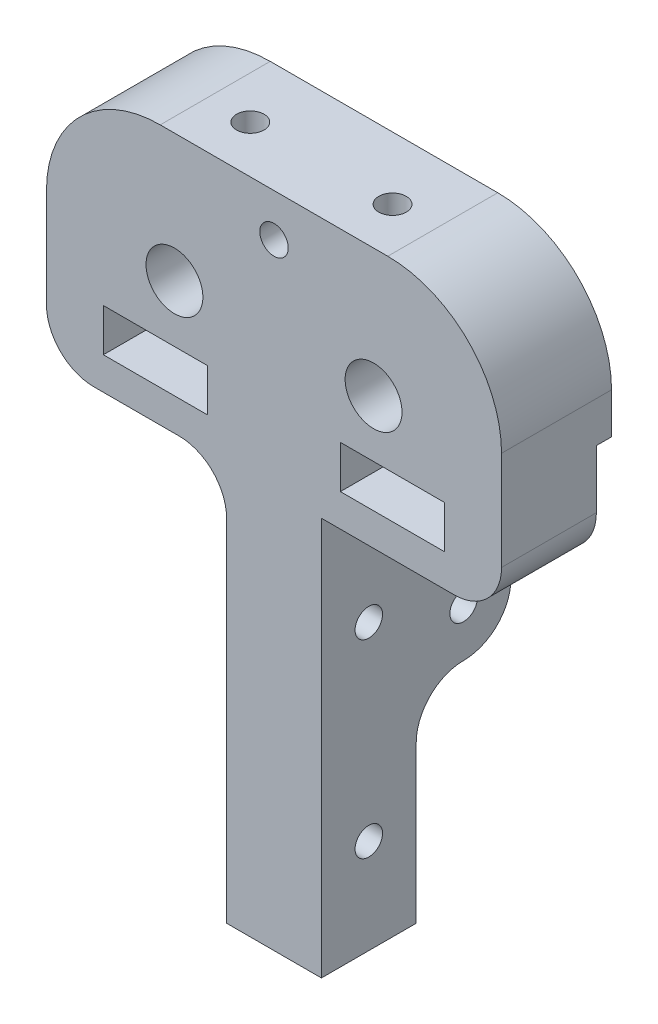
SolidWorks part; units mm, degrees
ref_plane "Front Plane" through (0, 0, 0) normal (0, 0, 1) x (1, 0, 0)
ref_plane "Top Plane" through (0, 0, 0) normal (0, 1, 0) x (1, 0, 0)
ref_plane "Right Plane" through (0, 0, 0) normal (1, 0, 0) x (0, 0, -1)
sketch "Sketch1" plane through (0, 0, 0) normal (0, 0, 1) x (1, 0, 0)
  line L1 (0, 0) -> (48, 0)
  line L2 (0, 0) -> (0, -70)
  line L3 (0, -70) -> (48, -70)
  line L4 (48, 0) -> (48, -70)
  dimension "D1" = 48
  dimension "D2" = 70
extrude "Boss-Extrude1" add sketch "Sketch1" along normal blind 10
sketch "Sketch2" plane through (0, 0, 10) normal (0, 0, 1) x (1, 0, 0)
  line L0 (0, 0) -> (0, -70) construction
  line L1 (48, 0) -> (0, 0) construction
  circle A0 centre (13.5, -13.5) radius 3
  circle A1 centre (34.5, -13.5) radius 3
  dimension "D1" = 6
  dimension "D2" = 6
  dimension "D3" = 21
  dimension "D4" = 13.5
  dimension "D5" = 13.5
  dimension "D6" = 13.5
extrude "Cut-Extrude1" cut sketch "Sketch2" against normal through all
sketch "Sketch3" plane through (0, 0, 10) normal (0, 0, 1) x (1, 0, 0)
  line L0 (0, 0) -> (0, -70) construction
  line L1 (13.7, -38.5) -> (34.3, -38.5)
  line L2 (13.7, -38.5) -> (13.7, -59.1)
  line L3 (13.7, -59.1) -> (34.3, -59.1)
  line L4 (34.3, -38.5) -> (34.3, -59.1)
  circle A0 centre (13.5, -13.5) radius 3 construction
  dimension "D1" = 20.6
  dimension "D2" = 20.6
  dimension "D3" = 13.7
  dimension "D4" = 25
extrude "Cut-Extrude2" cut sketch "Sketch3" against normal through all
fillet "Fillet1" radius 12 2 edges at (0, 0, 5) (48, 0, 5)
ref_plane "打印面" through (0, 0, -10) normal (0, 0, 1) x (1, 0, 0)
sketch "Sketch4" plane through (0, 0, 0) normal (0, 0, -1) x (-1, 0, 0)
  line L0 (-36, 0) -> (-12, 0) construction
  circle A0 centre (-24, -4.5) radius 1.5
  dimension "D1" = 3
  dimension "D2" = 4.5
extrude "Cut-Extrude3" cut sketch "Sketch4" against normal through all
sketch "Sketch5" plane through (0, 0, 0) normal (0, 1, 0) x (1, 0, 0)
  line L0 (36, -10) -> (12, -10) construction
  circle A0 centre (16.5, -5) radius 1.45
  circle A1 centre (31.5, -5) radius 1.45
  point P6 (24, -10)
  dimension "D1" = 2.9
  dimension "D3" = 5
  dimension "D4" = 7.5
extrude "Cut-Extrude4" cut sketch "Sketch5" against normal blind 10
sketch "Sketch7" plane through (0, 0, 0) normal (0, 0, -1) x (-1, 0, 0)
  line L0 (-48, -70) -> (-48, -12) construction
  line L1 (-42, -19.5) -> (-31, -19.5)
  line L2 (-42, -19.5) -> (-42, -24)
  line L3 (-42, -24) -> (-31, -24)
  line L4 (-31, -19.5) -> (-31, -24)
  line L5 (-24, 0) -> (-24, -28.6841) construction
  line L6 (-36, 0) -> (-12, 0) construction
  line L7 (-34.3, -38.5) -> (-13.7, -38.5) construction
  line L8 (-17, -19.5) -> (-17, -24)
  line L9 (-6, -24) -> (-17, -24)
  line L10 (-6, -19.5) -> (-6, -24)
  line L11 (-6, -19.5) -> (-17, -19.5)
  dimension "D1" = 4.5
  dimension "D2" = 11
  dimension "D3" = 6
  dimension "D4" = 14.5
extrude "Cut-Extrude5" cut sketch "Sketch7" against normal through all both and the other way through all
sketch "Sketch11" plane through (0, 0, 0) normal (0, 0, -1) x (-1, 0, 0)
  line L0 (-31, -24) -> (-42, -24) construction
  line L1 (-40, -27.5) -> (-8, -27.5)
  line L2 (-40, -27.5) -> (-40, -42.5)
  line L3 (-40, -42.5) -> (-8, -42.5)
  line L4 (-8, -27.5) -> (-8, -42.5)
  dimension "D1" = 15
  dimension "D2" = 3.5
  dimension "D3" = 2
  dimension "D4" = 2
extrude "Cut-Extrude6" cut sketch "Sketch11" against normal through all
sketch "Sketch12" plane through (0, -24, 0) normal (0, 1, 0) x (1, 0, 0)
  line L0 (31, 0) -> (42, 0) construction
  line L1 (6, 0) -> (17, 0) construction
  circle A0 centre (36.5, -3) radius 1.5
  circle A1 centre (11.5, -3) radius 1.5
  dimension "D1" = 3
  dimension "D3" = 3
extrude "Cut-Extrude7" cut sketch "Sketch12" against normal blind 5 and the other way blind 8
sketch "Sketch13" plane through (0, 0, 0) normal (0, 0, -1) x (-1, 0, 0)
  line L0 (-48, -70) -> (-48, -12) construction
  line L1 (-48, -16.3) -> (0, -16.3)
  line L2 (-48, -16.3) -> (-48, 0)
  line L3 (-48, 0) -> (0, 0)
  line L4 (0, -16.3) -> (0, 0)
  circle A0 centre (-34.5, -13.5) radius 3
  circle A1 centre (-13.5, -13.5) radius 3
  circle M10 centre (-24, -4.5) radius 1.5
  circle M19 centre (-34.5, -13.5) radius 3
  circle M20 centre (-13.5, -13.5) radius 3
  line M21 (0, -70) -> (0, -12)
  arc M22 (0, -12) -> (-12, 0) centre (-12, -12) ccw
  line M23 (-12, 0) -> (-36, 0)
  arc M24 (-36, 0) -> (-48, -12) centre (-36, -12) ccw
  line M25 (-48, -12) -> (-48, -70)
  dimension "D1" = 16.3
extrude "Boss-Extrude4" add sketch "Sketch13" along normal blind 1.6 contours L1 M25 M19 M20 M21 M22 M23 M24 M10 region at (24, -8.2505, 0)
fillet "Fillet2" radius 8 2 edges at (13.7, -42.5, 5) (34.3, -42.5, 5)
sketch "Sketch14" plane through (0, 0, 10) normal (0, 0, 1) x (1, 0, 0)
  line L0 (48, -70) -> (48, -12) construction
  line L1 (0, -70) -> (48, -70)
  line L2 (0, -70) -> (0, -27.4286)
  line L3 (0, -27.4286) -> (48, -27.4286)
  line L4 (48, -70) -> (48, -27.4286)
extrude "Cut-Extrude8" cut sketch "Sketch14" against normal through all
sketch "Sketch15" plane through (0, -27.4286, 0) normal (0, -1, 0) x (-1, 0, 0)
  line L0 (-48, 0) -> (0, 0) construction
  line L1 (-19, 0) -> (-29, 0)
  line L2 (-19, 0) -> (-19, -10)
  line L3 (-19, -10) -> (-29, -10)
  line L4 (-29, 0) -> (-29, -10)
  line L5 (-48, -10) -> (0, -10) construction
  point P8 (-24, 0)
  dimension "D1" = 10
  dimension "D2" = 24
extrude "Boss-Extrude5" add sketch "Sketch15" along normal blind 42
sketch "Sketch18" plane through (0, 0, 0) normal (0, 0, -1) x (-1, 0, 0)
  line L0 (-19, -69.4286) -> (-19, -27.4286) construction
  line L1 (-19, -37.9286) -> (-29, -37.9286)
  line L2 (-19, -37.9286) -> (-19, -47.9286)
  line L3 (-19, -47.9286) -> (-29, -47.9286)
  line L4 (-29, -37.9286) -> (-29, -47.9286)
  line L5 (-29, -69.4286) -> (-29, -27.4286) construction
  dimension "D1" = 10
  dimension "D2" = 21.5
extrude "Boss-Extrude8" add sketch "Sketch18" along normal blind 10
sketch "Sketch19" plane through (29, 0, 0) normal (1, 0, 0) x (0, 0, -1)
  line L0 (0, -69.4286) -> (-10, -69.4286) construction
  line L1 (10, -37.9286) -> (10, -47.9286) construction
  circle A0 centre (5, -42.9286) radius 1.45
  circle A1 centre (-5, -59.4286) radius 1.45
  circle A2 centre (-5, -39.4286) radius 1.45
  point P10 (10, -42.9286)
  dimension "D1" = 2.9
  dimension "D2" = 2.9
  dimension "D3" = 2.9
  dimension "D4" = 10
  dimension "D5" = 20
extrude "Cut-Extrude9" cut sketch "Sketch19" against normal through all
fillet "Fillet3" radius 5 3 edges at (0, -27.4286, 5) (19, -27.4286, 5) (48, -27.4286, 5)
fillet "Fillet4" radius 5 3 edges at (24, -47.9286, 0) (24, -47.9286, -10) (24, -37.9286, -10)
fillet "Fillet5" radius 2 1 edges at (24, -37.9286, 0)
equation "\"D3@Sketch3\"=(\"D1@Sketch1\"-\"D1@Sketch3\")/2"
equation "\"滑动-垂直孔\"= 0.6"
equation "\"滑动-水平孔\"= 0.3"
equation "\"松动-垂直孔\"= 0.3"
equation "\"松动-水平孔\"= 0.1"
equation "\"正常-垂直孔\"= 0.15"
equation "\"正常-水平孔\"= 0"
equation "\"紧缩-垂直孔\"= 0"
equation "\"紧缩-水平孔\"= - 0.1"
equation "\"D2@Sketch2\"=\"紧缩-垂直孔\"+6"
equation "\"D1@Sketch2\"=\"D2@Sketch2\""
equation "\"D2@Sketch3\"=\"滑动-垂直孔\"+20"
equation "\"D1@Sketch3\"=\"D2@Sketch3\""
equation "\"D4@Sketch3\"=19/2+20-6+1.5"
equation "\"D1@Sketch4\"=\"紧缩-垂直孔\"+3"
equation "\"D1@Sketch5\"=\"紧缩-水平孔\"+3"
equation "\"D3@Sketch5\"=\"D1@Boss-Extrude1\"/2"
equation "\"D4@Sketch5\"=7.5"
equation "\"D1@Sketch12\"=\"正常-水平孔\"+3"
equation "\"D3@Sketch12\"=\"D1@Sketch12\""
equation "\"D2@Sketch15\"=\"D1@Sketch1\"/2"
equation "\"D1@Sketch19\"=\"紧缩-水平孔\"+3"
equation "\"D2@Sketch19\"=\"D1@Sketch19\""
equation "\"D3@Sketch19\"=\"D1@Sketch19\""
